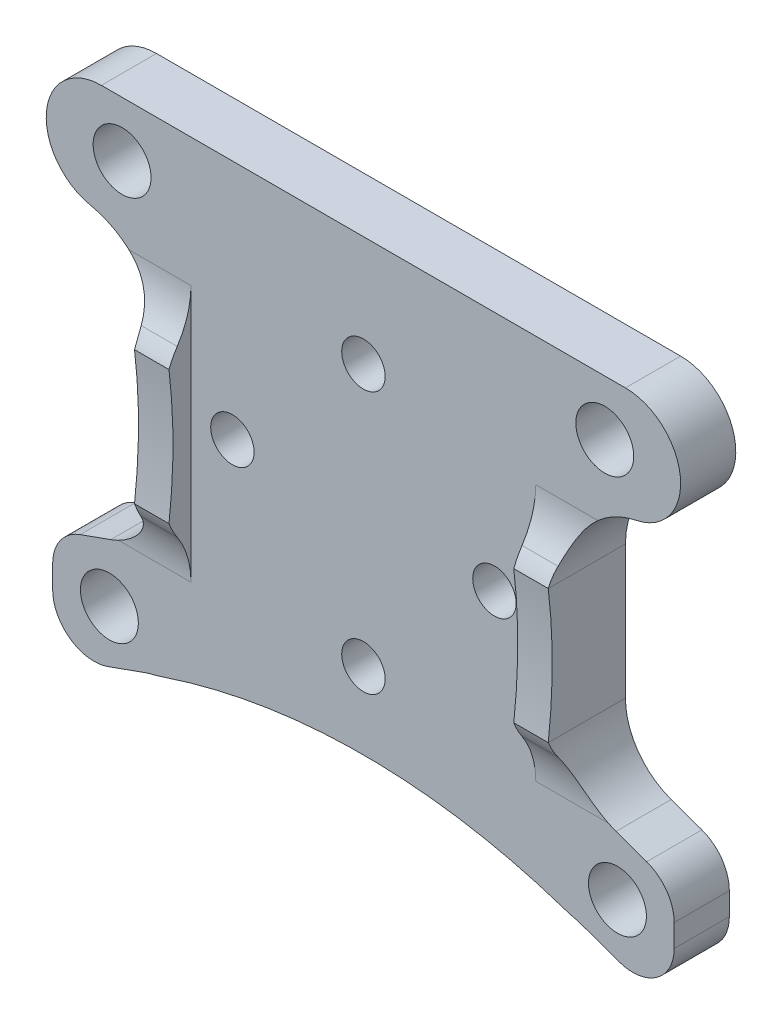
SolidWorks part; units mm, degrees
material "7075-T6 (SN)"
ref_plane "Ön Düzlem" through (0, 0, 0) normal (0, 0, 1) x (1, 0, 0)
ref_plane "Üst Düzlem" through (0, 0, 0) normal (0, 1, 0) x (1, 0, 0)
ref_plane "Sağ Düzlem" through (0, 0, 0) normal (1, 0, 0) x (0, 0, -1)
sketch "Çizim1" plane through (0, 0, 0) normal (0, 0, 1) x (1, 0, 0)
  line L1 (-14.1333, -17.5) -> (14.1333, -17.5)
  line L2 (-15, -5.9774) -> (-15, 9.5)
  line L3 (-15, 17.5) -> (15, 17.5)
  line L4 (15, -5.9774) -> (15, 9.5)
  line L5 (-15, -17.5) -> (15, 17.5) construction
  line L6 (-15, 17.5) -> (15, -17.5) construction
  line L7 (-15.8162, -17.7917) -> (-18.5235, -18.7594)
  line L8 (-18.3171, -10.6856) -> (-20.543, -11.4812)
  line L9 (-22.5333, -15.9344) -> (-22.5333, -14.3062)
  line L10 (0, -55) -> (0, 55) construction
  line L11 (15.8162, -17.7917) -> (18.5235, -18.7594)
  line L12 (22.5333, -15.9344) -> (22.5333, -14.3062)
  line L13 (18.3171, -10.6856) -> (20.543, -11.4812)
  line L14 (15, 9.5) -> (23, 9.5)
  line L15 (-15, 17.5) -> (-23, 17.5)
  line L17 (-15, 9.5) -> (-23, 9.5)
  line L18 (-23, 17.5) -> (-23, 9.5)
  line L19 (23, 17.5) -> (23, 9.5)
  line L20 (15, 17.5) -> (23, 17.5)
  arc A0 (-15, -5.9774) -> (-18.3171, -10.6856) centre (-20, -5.9774) cw
  arc A1 (-14.1333, -17.5) -> (-15.8162, -17.7917) centre (-14.1333, -22.5) ccw
  arc A2 (-18.5235, -18.7594) -> (-22.5333, -15.9344) centre (-19.5333, -15.9344) cw
  arc A3 (-20.543, -11.4812) -> (-22.5333, -14.3062) centre (-19.5333, -14.3062) ccw
  arc A4 (14.1333, -17.5) -> (15.8162, -17.7917) centre (14.1333, -22.5) cw
  arc A5 (18.5235, -18.7594) -> (22.5333, -15.9344) centre (19.5333, -15.9344) ccw
  arc A6 (15, -5.9774) -> (18.3171, -10.6856) centre (20, -5.9774) ccw
  arc A7 (20.543, -11.4812) -> (22.5333, -14.3062) centre (19.5333, -14.3062) cw
  point P0 (0, 0)
  point P11 (-15, -9.5)
  point P17 (-22.5333, -20.1926)
  point P20 (-22.5333, -12.1926)
  dimension "D5" = 5
  dimension "D6" = 5
  dimension "D7" = 3
  dimension "D1" = 30
  dimension "D2" = 35
  dimension "D3" = 8
  dimension "D4" = 8
  dimension "D8" = 8
  dimension "D9" = 8
extrude "Yükseklik-Ekstrüzyon1" add sketch "Çizim1" along normal blind 4
fillet "Radyus1" 2 edges at (23, 9.5, 2) (23, 17.5, 2) type full round first side face at (19, 9.5, 2) second side face at (0, 17.5, 2) middle face at (23, 13.5, 2)
fillet "Radyus2" 2 edges at (-23, 9.5, 2) (-23, 17.5, 2) type full round first side face at (-19, 9.5, 2) second side face at (-2, 17.5, 2) middle face at (-23, 13.5, 2)
sketch "Çizim2" plane through (0, 0, 0) normal (0, 0, -1) x (-1, 0, 0)
  circle A0 centre (0, 0) radius 9.5 construction
  point P3 (0, 9.5)
  point P7 (9.5, 0)
  point P8 (0, -9.5)
  point P9 (-9.5, 0)
  point P10 (0, 0)
  dimension "D1" = 19
hole_wizard "M3 Helisarmal için Zıvana matkabı1" positions "Çizim3" profile "Çizim4" hole size "M3x0.5" standard "ANSI Metric" end condition through all
sketch "Çizim3" plane through (0, 0, 0) normal (0, 0, -1) x (-1, 0, 0)
  point P0 (0, 9.5)
  point P3 (9.5, 0)
  point P6 (0, -9.5)
  point P9 (-9.5, 0)
sketch "Çizim4" plane through (0, 9.5, 0) normal (1, 0, 0) x (0, 1, 0)
  line L0 (0, 0) -> (0, 4)
  line L1 (0, 4) -> (1.575, 4)
  line L2 (1.575, 4) -> (1.575, 0)
  line L5 (1.575, 0) -> (0, 0)
  line L11 (0, -6.35) -> (0, 107.95) construction
  dimension "Thru Hole Dia." = 3.15
  dimension "Thru Hole Depth" = 4
sketch "Çizim5" plane through (0, 0, 0) normal (0, 0, -1) x (-1, 0, 0)
  line L0 (0, 2.2) -> (0, -2.2) construction
  circle A1 centre (-18.8837, -14.9121) radius 2 construction
  circle A2 centre (18.8837, -14.9121) radius 2 construction
  dimension "D1" = 4
fillet "Radyus3" radius 6 2 edges at (-15, 9.5, 2) (15, 9.5, 2)
sketch "Çizim8" plane through (15, 0, 0) normal (1, 0, 0) x (0, 0, -1)
  line L0 (-4, 3.702) -> (-4, -5.9774)
  line L1 (-4, 3.702) -> (-6, 3.702)
  line L2 (-4, -5.9774) -> (-6, -5.9774)
  line L3 (-6, 3.702) -> (-6, -5.9774)
  dimension "D1" = 2
extrude "Yükseklik-Ekstrüzyon2" add sketch "Çizim8" against normal blind 2.5
fillet "Radyus4" radius 6 2 edges at (13.75, 3.702, 4) (13.75, -5.9774, 4)
fillet "Radyus5" radius 6 2 edges at (13.75, -5.9774, 6) (13.75, 3.702, 6)
mirror "Aynalama1" about plane through (0, 0, 0) normal (1, 0, 0) of "Yükseklik-Ekstrüzyon2", "Radyus5", "Radyus4"
sketch "Çizim10" plane through (0, 0, 4) normal (0, 0, 1) x (1, 0, 0)
  line L0 (-14.9873, -17.5735) -> (14.9873, -17.5735)
  arc A0 (-14.9873, -17.5735) -> (14.9873, -17.5735) centre (0, -60.6858) cw
  arc A1 (-14.1333, -17.5) -> (-15.8162, -17.7917) centre (-14.1333, -22.5) ccw construction
  arc A2 (15.8162, -17.7917) -> (14.1333, -17.5) centre (14.1333, -22.5) ccw construction
extrude "Kes-Ekstrüzyon6" cut sketch "Çizim10" against normal through all
fillet "Radyus12" radius 10 2 edges at (14.9873, -17.5735, 2) (-14.9873, -17.5735, 2)
sketch "Çizim11" plane through (15, 0, 0) normal (1, 0, 0) x (0, 0, -1)
  line L0 (-6, 1.5409) -> (-6, -3.8162) construction
  line L1 (-6, 1.5409) -> (-6, -3.8162)
  arc A0 (-5.5973, 3.702) -> (-5.5973, -5.9774) centre (-46.0143, -1.1377) cw
  arc A1 (-5.5973, 3.702) -> (-6, 1.5409) centre (0, 1.5409) ccw construction
  arc A2 (-6, -3.8162) -> (-5.5973, -5.9774) centre (0, -3.8162) ccw construction
  arc A3 (-5.5973, 3.702) -> (-6, 1.5409) centre (0, 1.5409) ccw
  arc A4 (-6, -3.8162) -> (-5.5973, -5.9774) centre (0, -3.8162) ccw
extrude "Kes-Ekstrüzyon7" cut sketch "Çizim11" against normal through all
sketch "Çizim15" plane through (0, 0, 0) normal (0, 0, -1) x (-1, 0, 0)
  line L0 (-19, 13.5) -> (-17.5, 13.5) construction
  line L1 (0, 3.3) -> (0, -3.3) construction
  line L2 (19, 13.5) -> (17.5, 13.5) construction
  line L3 (-19.5333, -15.9344) -> (-18.4199, -14.9293) construction
  line L4 (19.5333, -15.9344) -> (18.4199, -14.9293) construction
  dimension "D1" = 1.5
  dimension "D2" = 1.5
hole_wizard "M4 Helisarmal için Zıvana matkabı3" positions "Çizim16" profile "Çizim17" hole size "M4x0.7" standard "ANSI Metric" end condition through all
sketch "Çizim16" plane through (0, 0, 0) normal (0, 0, -1) x (-1, 0, 0)
  point P0 (-17.5, 13.5)
  point P3 (17.5, 13.5)
  point P6 (-18.4199, -14.9293)
  point P9 (18.4199, -14.9293)
sketch "Çizim17" plane through (17.5, 13.5, 0) normal (1, 0, 0) x (0, 1, 0)
  line L0 (0, 0) -> (0, 5.5973)
  line L1 (0, 5.5973) -> (2.1, 5.5973)
  line L2 (2.1, 5.5973) -> (2.1, 0)
  line L5 (2.1, 0) -> (0, 0)
  line L11 (0, -6.35) -> (0, 107.95) construction
  dimension "Thru Hole Dia." = 4.2
  dimension "Thru Hole Depth" = 5.5973
ref_plane "Düzlem1" through (0, 0, 3) normal (0, 0, 1) x (1, 0, 0)
